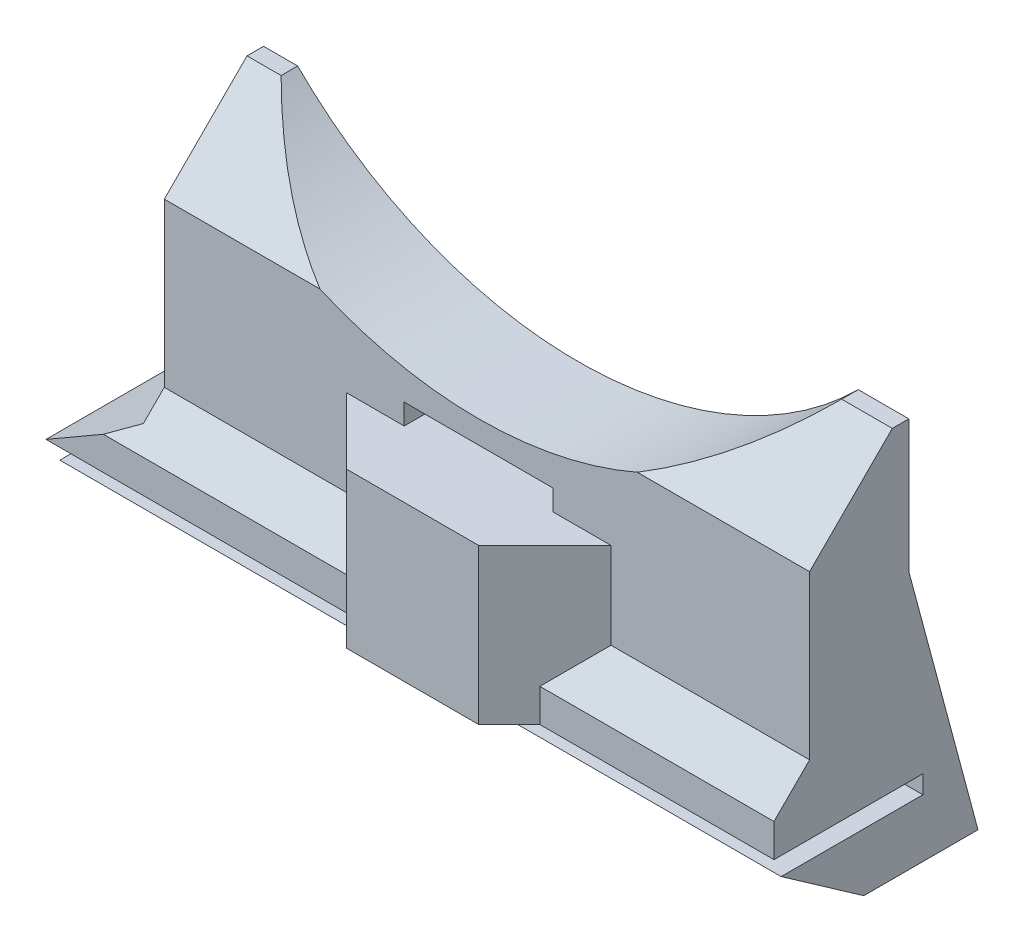
SolidWorks part; units mm, degrees
material "ABS"
ref_plane "Front Plane" through (0, 0, 0) normal (0, 0, 1) x (1, 0, 0)
ref_plane "Top Plane" through (0, 0, 0) normal (0, 1, 0) x (1, 0, 0)
ref_plane "Right Plane" through (0, 0, 0) normal (1, 0, 0) x (0, 0, -1)
sketch "Sketch1" plane through (0, 0, 0) normal (1, 0, 0) x (0, 0, -1)
  line L0 (0, -6) -> (4, -6)
  line L1 (0, -6) -> (-8.5689, 0)
  line L2 (-8.5689, 0) -> (0, 0)
  line L3 (0, 0) -> (0, 1.1)
  line L4 (0, 1.1) -> (-9, 1.1)
  line L5 (-9, 1.1) -> (-9, 3.1)
  line L6 (-6.8499, 12.1) -> (-0.8499, 12.1)
  line L7 (4, -6) -> (-0.8499, 12.1)
  line L8 (-9, 3.1) -> (-6.8499, 5.2501)
  line L9 (-6.8499, 5.2501) -> (-6.8499, 12.1)
  line L10 (-9, 3.1) -> (-9, 12.1) construction
  line L11 (-9, 12.1) -> (-6.8499, 12.1) construction
  dimension "D1" = 6
  dimension "D2" = 35
  dimension "D3" = 4
  dimension "D4" = 105
  dimension "D5" = 1.1
  dimension "D6" = 11
  dimension "D7" = 9
  dimension "D8" = 6
  dimension "D9" = 45
  dimension "D10" = 2
extrude "Boss-Extrude1" add sketch "Sketch1" along normal mid plane 40
sketch "Sketch3" [suppressed] plane through (0, 11.2, 0) normal (0, 1, 0) x (1, 0, 0)
  arc A0 (25, -14.2381) -> (32.5, -21.7381) centre (32.5, -14.2381) ccw construction
  circle A2 centre (32.5, -14.2381) radius 1.75
  point P0 (32.5, -14.2381)
  dimension "D1" = 3.5
extrude "Cut-Extrude1" [suppressed] cut sketch "Sketch3" against normal through all
sketch "Sketch4" [suppressed] plane through (0, 11.2, 0) normal (0, 1, 0) x (1, 0, 0)
  line L1 (35.375, -12.5782) -> (32.5, -10.9184)
  line L2 (32.5, -10.9184) -> (29.625, -12.5782)
  line L3 (29.625, -12.5782) -> (29.625, -15.898)
  line L4 (29.625, -15.898) -> (32.5, -17.5579)
  line L5 (32.5, -17.5579) -> (35.375, -15.898)
  line L6 (35.375, -15.898) -> (35.375, -12.5782)
  arc A0 (25, -14.2381) -> (32.5, -21.7381) centre (32.5, -14.2381) ccw construction
  circle A1 centre (32.5, -14.2381) radius 2.875 construction
  point P0 (32.5, -14.2381)
  dimension "D1" = 5.75
extrude "Cut-Extrude2" [suppressed] cut sketch "Sketch4" against normal blind 3
chamfer "Chamfer2" [suppressed] distance 1 angle 45 tangent propagation no
sketch "Sketch5" plane through (20, 0, 0) normal (1, 0, 0) x (0, 0, -1)
  line L0 (-10, 11.2) -> (-10, 18.7)
  line L1 (-0.8499, 12.1) -> (-6.8499, 12.1) construction
  line L2 (-10, 18.7) -> (-1.4273, 18.7)
  line L3 (-1.4273, 18.7) -> (-0.8499, 12.1)
  line L4 (-0.8499, 12.1) -> (-6.8499, 12.1) construction
  line L12 (-9, 3.1) -> (-9, 1.1)
  line L14 (0, -6) -> (4, -6)
  line L16 (4, -6) -> (-0.8499, 12.1)
  line L17 (-0.8499, 12.1) -> (-6.8499, 12.1)
  line L19 (-9, 1.1) -> (0, 1.1)
  line L20 (0, 1.1) -> (0, 0)
  line L21 (0, 0) -> (-8.5689, 0)
  line L22 (-6.8499, 12.1) -> (-6.8499, 5.2501)
  line L23 (-8.5689, 0) -> (0, -6)
  line L24 (-6.8499, 12.1) -> (-6.8499, 5.2501)
  line L25 (-6.8499, 5.2501) -> (-9, 3.1)
  line L26 (-6.8499, 5.2501) -> (-9, 3.1)
  line L27 (-0.8499, 12.1) -> (-7.6654, 12.1)
  dimension "D1" = 85
  dimension "D2" = 7.5
  dimension "D4" = 0
extrude "Boss-Extrude3" [suppressed] add sketch "Sketch5" against normal up to surface (40 mm away)
sketch "Sketch6" [suppressed] plane through (0, 0, 9) normal (0, 0, 1) x (1, 0, 0)
  line L1 (0, 18.7) -> (40, 18.7) construction
  line L2 (40, 1.2) -> (0.0849, 1.2) construction
  circle A0 centre (20, 36.2) radius 24
  point P4 (20, 18.7)
  point P5 (20, 12.2)
  dimension "D1" = 48
  dimension "D2" = 11
extrude "Cut-Extrude3" [suppressed] cut sketch "Sketch6" against normal through all
chamfer "Chamfer3" [suppressed] distance 1 angle 45
sketch "Sketch7" plane through (0, 0, 6.8499) normal (0, 0, 1) x (1, 0, 0)
  line L0 (0, 12.1) -> (0, 13.1) construction
  line L1 (20, 12.1) -> (-20, 12.1) construction
  line L2 (-20, 12.1) -> (-20, 20.1)
  line L3 (20, 12.1) -> (-20, 12.1)
  line L4 (-20, 20.1) -> (-16.9411, 20.1)
  line L5 (20, 20.1) -> (16.9411, 20.1)
  line L6 (20, 12.1) -> (20, 20.1)
  line L7 (20, 1.1) -> (-20, 1.1) construction
  line L8 (20, 12.1) -> (-20, 12.1) construction
  arc A0 (16.9411, 20.1) -> (-16.9411, 20.1) centre (0, 37.1) cw
  dimension "D1" = 8
  dimension "D2" = 24
  dimension "D3" = 12
extrude "Boss-Extrude4" add sketch "Sketch7" against normal up to vertex (6 mm away) up to point (20, 12.1, 0.8499)
ref_plane "Plane1" through (0, 13.1, 0) normal (0, 1, 0) x (1, 0, 0)
ref_plane "Plane2" through (0, 10.6, 0) normal (0, 1, 0) x (1, 0, 0)
ref_plane "Plane5" through (-2.5, 0, 0) normal (1, 0, 0) x (0, 0, -1)
ref_axis "Axis2" through (-2.5, 10.6, -5.7856) along (0, 0, 1)
ref_plane "Plane3" through (0, 0, 3.8499) normal (0, 0, -1) x (-1, 0, 0)
ref_plane "Plane4" through (0, 0, -0.1501) normal (0, 0, -1) x (-1, 0, 0)
chamfer "Chamfer4" distance 5 angle 45 2 edges at (-18.4705, 20.1, 6.8499) (18.4705, 20.1, 6.8499)
sketch "Sketch15" plane through (-20, 0, 0) normal (-1, 0, 0) x (0, 0, 1)
  line L10 (9, 1.1) -> (9, 3.1)
  line L11 (6.8499, 15.1) -> (1.8499, 20.1)
  line L13 (0.8499, 20.1) -> (0.8499, 12.1)
  line L14 (0.8499, 12.1) -> (-4, -6)
  line L15 (-4, -6) -> (0, -6)
  line L16 (0, -6) -> (8.5689, 0)
  line L17 (8.5689, 0) -> (0, 0)
  line L18 (0, 0) -> (0, 1.1)
  line L19 (0, 1.1) -> (9, 1.1)
  line L20 (9, 1.1) -> (9, 3.1)
  line L21 (6.8499, 15.1) -> (1.8499, 20.1)
  line L23 (0.8499, 20.1) -> (0.8499, 12.1)
  line L24 (0.8499, 12.1) -> (-4, -6)
  line L25 (-4, -6) -> (0, -6)
  line L26 (0, -6) -> (8.5689, 0)
  line L27 (8.5689, 0) -> (0, 0)
  line L28 (0, 0) -> (0, 1.1)
  line L29 (0, 1.1) -> (9, 1.1)
  line L30 (1.8499, 20.1) -> (0.8499, 20.1)
  line L31 (1.8499, 20.1) -> (0.8499, 20.1)
  line L34 (6.8499, 5.2501) -> (6.8499, 15.1)
  line L35 (6.8499, 5.2501) -> (6.8499, 15.1)
  line L36 (9, 3.1) -> (6.8499, 5.2501)
  line L37 (9, 3.1) -> (6.8499, 5.2501)
  dimension "D1" = 0
extrude "Boss-Extrude5" add sketch "Sketch15" along normal blind 4
sketch "Sketch16" plane through (0, 0, 0) normal (0, 0, 1) x (1, 0, 0)
  line L0 (-24, 1.1) -> (-19, 3.9868)
  line L1 (-19, 3.9868) -> (-19, 20.1)
  line L2 (-24, 20.1) -> (-16.9411, 20.1) construction
  line L3 (20, 1.1) -> (-24, 1.1) construction
  line L4 (-19, 20.1) -> (-24, 20.1)
  line L5 (-24, 20.1) -> (-24, 1.1)
  dimension "D1" = 30
  dimension "D2" = 5
extrude "Cut-Extrude4" cut sketch "Sketch16" against normal through all and the other way through all
fillet "Fillet1" radius 10 1 edges at (-24, -6, -2)
chamfer "Chamfer5" distance 2.5 angle 45 1 edges at (20, -6, -2)
sketch "Sketch17" plane through (0, 0, 0) normal (0, 0, 1) x (1, 0, 0)
  line L1 (-4.5, 11.725) -> (4.5, 11.725)
  line L2 (-4.5, 11.725) -> (-4.5, 10.475)
  line L3 (-4.5, 10.475) -> (4.5, 10.475)
  line L4 (4.5, 11.725) -> (4.5, 10.475)
  line L5 (-4.5, 11.725) -> (4.5, 10.475) construction
  line L6 (-4.5, 10.475) -> (4.5, 11.725) construction
  arc A0 (-16.9411, 20.1) -> (16.9411, 20.1) centre (0, 37.1) ccw construction
  point P0 (0, 11.1)
  point P5 (0, 13.1)
  dimension "D1" = 9
  dimension "D2" = 1.25
  dimension "D3" = 2
extrude "Cut-Extrude5" cut sketch "Sketch17" along normal through all
sketch "Sketch18" plane through (0, 0, 6.8499) normal (0, 0, 1) x (1, 0, 0)
  line L0 (-4.5, 10.475) -> (4.5, 10.475) construction
  line L1 (-4, 10.475) -> (4, 10.475)
  line L2 (-4, 10.475) -> (-4, 1.1)
  line L3 (-4, 1.1) -> (4, 1.1)
  line L4 (4, 10.475) -> (4, 1.1)
  line L6 (20, 1.1) -> (-24, 1.1) construction
  point P4 (0, 10.475)
  point P7 (0, 10.475)
  dimension "D1" = 8
extrude "Boss-Extrude6" add sketch "Sketch18" along normal blind 4
sketch "Sketch19" plane through (0, 10.475, 0) normal (0, 1, 0) x (1, 0, 0)
  line L0 (0, -6.8499) -> (0, -10.8499) construction
  line L1 (-9.5917, -6.8499) -> (9.5917, -6.8499) construction
  line L2 (4, -10.8499) -> (-4, -10.8499) construction
  line L3 (4, -6.8499) -> (4, -10.8499)
  line L4 (4, -10.8499) -> (8, -6.8499)
  line L5 (20, -6.8499) -> (4, -6.8499) construction
  line L6 (4, -6.8499) -> (8, -6.8499)
  line L7 (-4, -6.8499) -> (-8, -6.8499)
  line L8 (-4, -10.8499) -> (-8, -6.8499)
  line L9 (-4, -6.8499) -> (-4, -10.8499)
extrude "Boss-Extrude8" add sketch "Sketch19" against normal up to surface (9.375 mm away) up to face at (-1, 1.1, 7.2125)
